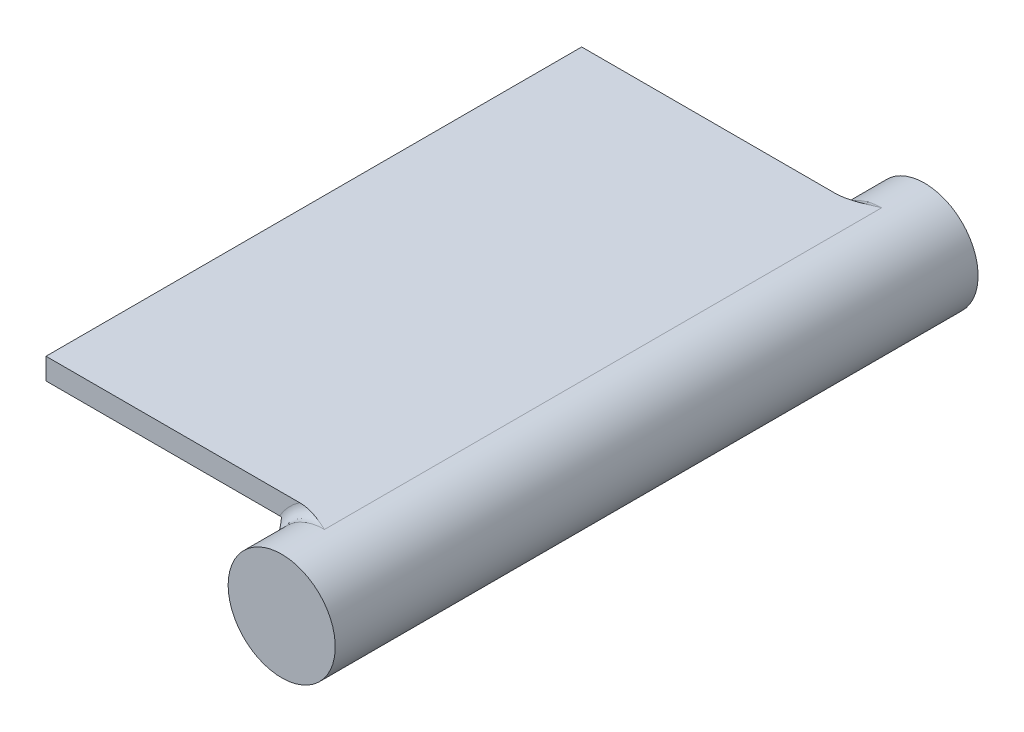
SolidWorks part; units mm, degrees
ref_plane "Front Plane" through (0, 0, 0) normal (0, 0, 1) x (1, 0, 0)
ref_plane "Top Plane" through (0, 0, 0) normal (0, 1, 0) x (1, 0, 0)
ref_plane "Right Plane" through (0, 0, 0) normal (1, 0, 0) x (0, 0, -1)
sketch "Sketch1" plane through (0, 0, 0) normal (0, 0, 1) x (1, 0, 0)
  line L1 (-16, -5) -> (16, -5)
  line L2 (-16, -5) -> (-16, 5)
  line L3 (-16, 5) -> (16, 5)
  line L4 (16, -5) -> (16, 5)
  line L5 (-16, -5) -> (16, 5) construction
  line L6 (-16, 5) -> (16, -5) construction
  point P0 (0, 0)
  dimension "D1" = 32
  dimension "D2" = 10
extrude "Boss-Extrude1" add sketch "Sketch1" along normal mid plane 50
fillet "Fillet1" radius 5 2 edges at (16, -5, 0) (16, 5, 0)
sketch "Sketch2" plane through (0, 0, -25) normal (0, 0, -1) x (-1, 0, 0)
  circle A0 centre (-11, 0) radius 5
  dimension "D1" = 10
extrude "Boss-Extrude2" add sketch "Sketch2" along normal blind 5
sketch "Sketch3" plane through (0, 0, -25) normal (0, 0, -1) x (-1, 0, 0)
  line L5 (16, 5) -> (16, -5) construction
  line L6 (16, 0) -> (16, -5)
  line L7 (16, -5) -> (-11, -5)
  line L8 (-6, 0) -> (-6, 3)
  line L9 (-6, 3) -> (16, 3)
  line L10 (16, 3) -> (16, 0)
  line L11 (-11, 5) -> (16, 5) construction
  arc A1 (-11, -5) -> (-6, 0) centre (-11, 0) ccw
  dimension "D1" = 90
  dimension "D2" = 2
  dimension "D3" = 0
extrude "Cut-Extrude1" cut sketch "Sketch3" against normal through all
sketch "Sketch5" plane through (0, 0, 0) normal (0, 0, 1) x (1, 0, 0)
  line L0 (-16, 3) -> (6, 0)
  line L1 (6, 0) -> (6, 3)
  line L2 (6, 3) -> (-16, 3)
extrude "Boss-Extrude3" add sketch "Sketch5" along normal blind 8 and the other way blind 8
mirror "Mirror1" about plane through (0, 0, 0) normal (0, 0, 1) of "Boss-Extrude2"
sketch "Sketch7" plane through (0, 0, -30) normal (0, 0, -1) x (-1, 0, 0)
  line L0 (-13.6458, 3) -> (-8.3542, 3)
  line L1 (-11, 0) -> (-11, 4) construction
  line L2 (17.6, 0) -> (-17.6, 0) construction
  arc A0 (-13.6458, 3) -> (-8.3542, 3) centre (-11, 0) ccw
  point P8 (-11, 0)
  dimension "D2" = 8
  dimension "D1" = 3
extrude "Cut-Extrude2" cut sketch "Sketch7" against normal blind 8.5
fillet "Fillet2" radius 1 2 edges at (7.4645, 3.5355, 25) (7.4645, 3.5355, -25)
fillet "Fillet4" radius 1 2 edges at (6, 1.5, -8) (6, 1.5, 8)
